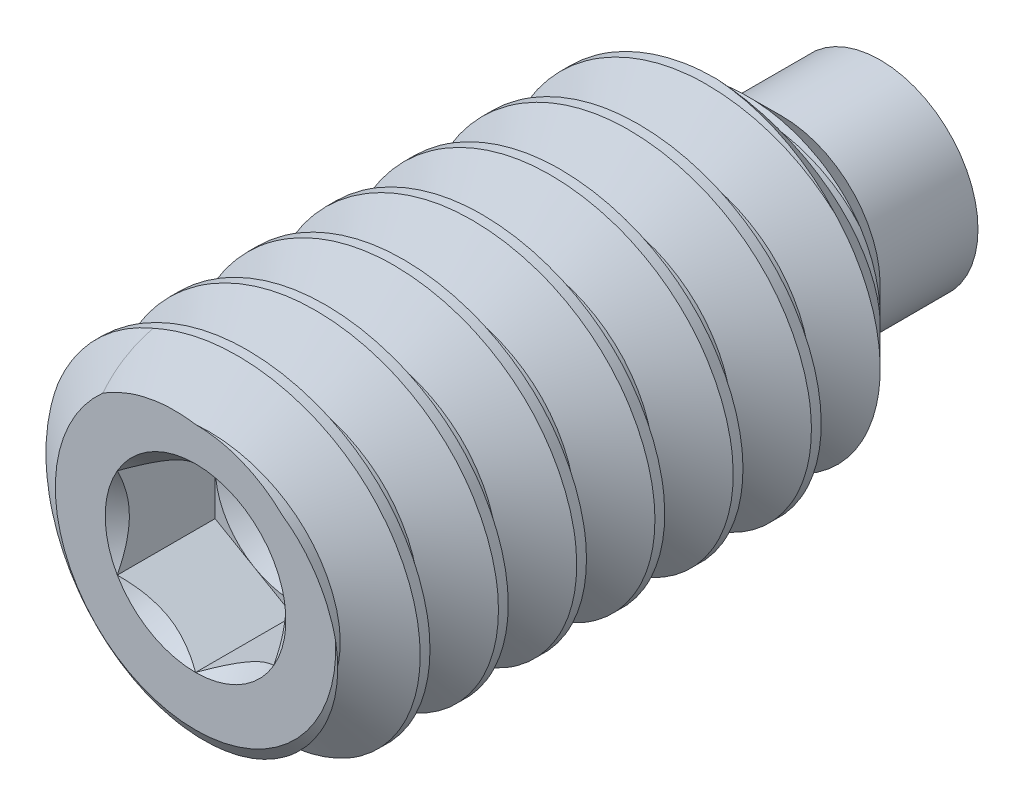
SolidWorks part; units mm, degrees
material "Cast Alloy Steel"
ref_plane "Front" through (0, 0, 0) normal (0, 0, 1) x (1, 0, 0)
ref_plane "Top" through (0, 0, 0) normal (0, 1, 0) x (1, 0, 0)
ref_plane "Right" through (0, 0, 0) normal (1, 0, 0) x (0, 0, -1)
sketch "Sketch22" plane through (0, 0, 0) normal (1, 0, 0) x (0, 0, -1)
  line L0 (-2.7781, 0) -> (-2.7781, 1.1379)
  line L1 (-2.7781, 1.1379) -> (-2.5789, 1.4224)
  line L2 (-2.5789, 1.4224) -> (1.3557, 1.4224)
  line L3 (1.3557, 1.4224) -> (1.9844, 0.7938)
  line L4 (-2.7781, 1.1379) -> (-2.7781, -1.1379) construction
  line L5 (2.7781, 0) -> (-2.7781, 0)
  line L6 (0, 1.4224) -> (0, -1.4224) construction
  line L8 (1.9844, 0.7938) -> (2.7781, 0.7938)
  line L9 (-1.9673, -1.4224) -> (1.9673, -1.4224) construction
  line L10 (2.7781, 0.7938) -> (2.7781, 0)
  line L11 (2.7781, 0.7938) -> (2.7781, -0.7937) construction
  dimension "D1" = 45
  dimension "Dia" = 2.8448
  dimension "D2" = 2.2758
  dimension "Length" = 4.7625
  dimension "D3" = 35
  dimension "A" = 1.5875
  dimension "B" = 0.7937
revolve "Revolve1" add sketch "Sketch22" angle 360 about L5
ref_plane "Plane1" through (0, 0, -1.9844) normal (0, 0, 1) x (1, 0, 0)
sketch "Sketch27" plane through (0, 0, -1.9844) normal (0, 0, 1) x (1, 0, 0)
  circle A0 centre (0, 0) radius 1.4224 construction
  circle A1 centre (0, 0) radius 1.4224
curve "Helix/Spiral1" pitch 0.635 height 6.0325 radius 1.4224 centre (0, 0, -1.9844) axis (0, 0, 1) start towards (0, 1, 0)
sketch "Sketch28" plane through (0, 0, 0) normal (1, 0, 0) x (0, 0, -1)
  line L0 (1.9844, 1.4224) -> (2.54, 1.4224)
  line L1 (2.54, 1.4224) -> (2.3019, 1.01)
  line L2 (2.3019, 1.01) -> (2.2225, 1.01)
  line L3 (2.2225, 1.01) -> (1.9844, 1.4224)
  line L4 (2.1034, 1.2162) -> (2.4209, 1.2162) construction
  line L6 (-2.5789, 1.4224) -> (1.3557, 1.4224) construction
  line L7 (1.9844, 1.5646) -> (1.9844, -1.5646) construction
  dimension "D1" = 0.0794
  dimension "D2" = 0.3175
  dimension "D3" = 60
sweep "Cut-Sweep2" cut profiles "Sketch28" path "Helix/Spiral1"
sketch "Sketch23" plane through (0, 0, 2.7781) normal (0, 0, 1) x (1, 0, 0)
  line L1 (0, 0.7332) -> (-0.635, 0.3666)
  line L2 (-0.635, 0.3666) -> (-0.635, -0.3666)
  line L3 (-0.635, -0.3666) -> (0, -0.7332)
  line L4 (0, -0.7332) -> (0.635, -0.3666)
  line L5 (0.635, -0.3666) -> (0.635, 0.3666)
  line L6 (0.635, 0.3666) -> (0, 0.7332)
  circle A0 centre (0, 0) radius 0.635 construction
  dimension "Hex" = 1.27
extrude "Cut-Extrude10" cut sketch "Sketch23" against normal blind 0.7937
sketch "Sketch24" plane through (0, 0, 2.7781) normal (0, 0, 1) x (1, 0, 0)
  circle A0 centre (0, 0) radius 0.7332
extrude "Cut-Extrude11" cut sketch "Sketch24" against normal through all draft 45
sketch "Sketch26" plane through (0, 0, 1.9844) normal (0, 0, 1) x (1, 0, 0)
  circle A0 centre (0, 0) radius 0.635 construction
  circle A1 centre (0, 0) radius 0.635
extrude "Cut-Extrude12" cut sketch "Sketch26" against normal through all draft 60
sketch "Sketch30" plane through (0, 0, 0) normal (1, 0, 0) x (0, 0, -1)
  line L0 (-2.5789, 1.4224) -> (1.3557, 1.4224) construction
  line L1 (-2.7781, 0) -> (-2.7781, 1.1379) construction
  line L2 (1.9844, 1.4224) -> (1.9844, -1.4224) construction
  line L3 (-1.9673, -1.4224) -> (1.9673, -1.4224) construction
  point P0 (-2.7781, 1.4224)
  point P1 (2.7781, 1.4224)
  point P2 (2.7781, -1.4224)
  point P11 (-0.2381, -1.4224)
  dimension "D1" = 2.2225
equation "\"D1@Sketch28\" = \"D4@Helix/Spiral1\" * .125"
equation "\"D3@Helix/Spiral1\" = \"Length@Sketch22\" +  ( \"D4@Helix/Spiral1\" * 2 ) "
equation "\"D1@Sketch30\" = \"D4@Helix/Spiral1\" * 3.5"
equation "\"hex Depth@Cut-Extrude10\" = \"Hex@Sketch23\" * .625"
equation "\"D2@Sketch28\" = \"D4@Helix/Spiral1\" * .5"
equation "\"D2@Sketch22\" = \"Dia@Sketch22\" * .8"
